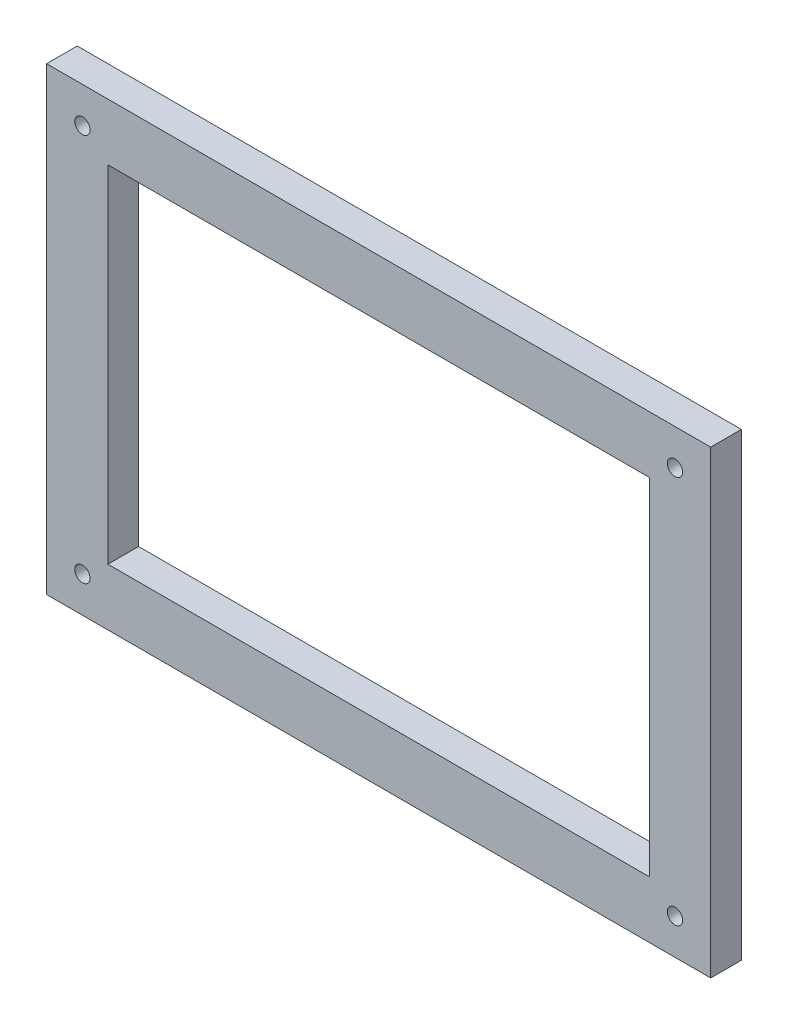
SolidWorks part; units mm, degrees
ref_plane "Płaszczyzna przednia" through (0, 0, 0) normal (0, 0, 1) x (1, 0, 0)
ref_plane "Płaszczyzna górna" through (0, 0, 0) normal (0, 1, 0) x (1, 0, 0)
ref_plane "Płaszczyzna prawa" through (0, 0, 0) normal (1, 0, 0) x (0, 0, -1)
sketch "Sketch1" plane through (0, 0, 0) normal (0, 0, 1) x (1, 0, 0)
  line L1 (0, 0) -> (106, 0)
  line L2 (0, 0) -> (0, 67.7)
  line L3 (0, 67.7) -> (106, 67.7)
  line L4 (106, 0) -> (106, 67.7)
  line L5 (0, 0) -> (106, 67.7) construction
  line L6 (0, 67.7) -> (106, 0) construction
  line L7 (-12, -11.15) -> (118, -11.15)
  line L8 (-12, -11.15) -> (-12, 78.85)
  line L9 (-12, 78.85) -> (118, 78.85)
  line L10 (118, -11.15) -> (118, 78.85)
  line L11 (-12, -11.15) -> (118, 78.85) construction
  line L12 (-12, 78.85) -> (118, -11.15) construction
  point P4 (53, 33.85)
  point P10 (53, 33.85)
  dimension "D1" = 106
  dimension "D2" = 67.7
  dimension "D3" = 90
  dimension "D4" = 130
  dimension "D5" = 12
  dimension "D6" = 11.15
extrude "Boss-Extrude1" add sketch "Sketch1" along normal blind 6
hole_wizard "Ø3.0mm Dowel Hole1" positions "Sketch2" profile "Sketch3" hole size "Ø3.0" standard "ANSI Metric" end condition up to next
sketch "Sketch2" plane through (0, 0, 6) normal (0, 0, 1) x (1, 0, 0)
  line L0 (118, -11.15) -> (118, 78.85) construction
  line L1 (118, 78.85) -> (-12, 78.85) construction
  line L2 (-12, -11.15) -> (118, -11.15) construction
  line L3 (-12, 78.85) -> (-12, -11.15) construction
  point P0 (111, 71.85)
  point P3 (111, -4.15)
  point P5 (-5, -4.15)
  point P7 (-5, 71.85)
  dimension "D1" = 7
  dimension "D2" = 7
  dimension "D3" = 7
  dimension "D4" = 7
  dimension "D5" = 7
  dimension "D6" = 7
  dimension "D7" = 7
  dimension "D8" = 7
sketch "Sketch3" plane through (111, 71.85, 6) normal (1, 0, 0) x (0, -1, 0)
  line L0 (0, 0) -> (0, 6)
  line L1 (0, 6) -> (1.5, 6)
  line L2 (1.5, 6) -> (1.5, 0)
  line L5 (1.5, 0) -> (0, 0)
  line L11 (0, -6.35) -> (0, 107.95) construction
  dimension "Thru Hole Dia." = 3
  dimension "Thru Hole Depth" = 6
